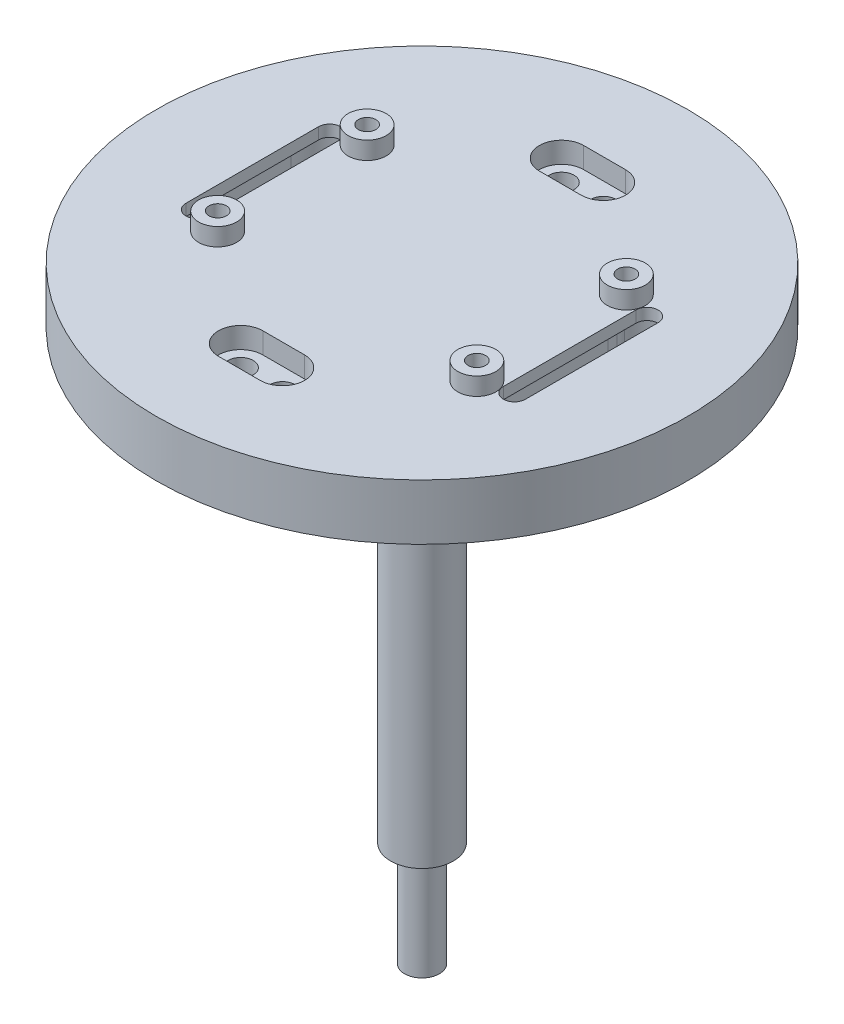
SolidWorks part; units mm, degrees
ref_plane "Front Plane" through (0, 0, 0) normal (0, 0, 1) x (1, 0, 0)
ref_plane "Top Plane" through (0, 0, 0) normal (0, 1, 0) x (1, 0, 0)
ref_plane "Right Plane" through (0, 0, 0) normal (1, 0, 0) x (0, 0, -1)
sketch "Sketch1" plane through (0, 0, 0) normal (0, 0, 1) x (1, 0, 0)
  line L0 (0, 0) -> (0, 87) construction
  line L1 (0, 87) -> (38.1, 87)
  line L2 (38.1, 87) -> (38.1, 79)
  line L3 (38.1, 79) -> (15, 79)
  line L4 (15, 79) -> (15, 80)
  line L5 (15, 80) -> (4.5, 80)
  line L6 (4.5, 80) -> (4.5, 15)
  line L7 (4.5, 15) -> (2.5, 15)
  line L8 (2.5, 15) -> (2.5, 0)
  line L9 (2.5, 0) -> (0, 0)
  line L10 (0, 0) -> (0, 87)
  dimension "D1" = 79
  dimension "D2" = 5
  dimension "D3" = 9
  dimension "D4" = 1
  dimension "D5" = 30
  dimension "D6" = 8
  dimension "D7" = 76.2
  dimension "D8" = 15
revolve "Revolve1" add sketch "Sketch1" angle 360 about L0
hole_wizard "CBORE for M3 SHCS1" positions "Sketch2" profile "Sketch3" counterbore size "M3" standard "ANSI Metric" end condition through all
sketch "Sketch2" plane through (0, 87, 0) normal (0, 1, 0) x (1, 0, 0)
  line L0 (0, 0) -> (0, 23) construction
  line L1 (0, 23) -> (3, 23) construction
  line L3 (0, 23) -> (-3, 23) construction
  line L5 (-3, -23) -> (0, -23) construction
  line L6 (0, -23) -> (0, 0) construction
  line L8 (0, -23) -> (3, -23) construction
  point P0 (3, 23)
  point P11 (-3, 23)
  point P14 (-3, -23)
  point P21 (3, -23)
  dimension "D1" = 46
  dimension "D2" = 6
sketch "Sketch3" plane through (3, 87, -23) normal (1, 0, 0) x (0, 0, 1)
  line L0 (0, 0) -> (0, 87)
  line L1 (0, 87) -> (1.8, 87)
  line L3 (1.8, 87) -> (1.8, 3)
  line L4 (1.8, 3) -> (3.175, 3)
  line L5 (3.175, 3) -> (3.175, 0)
  line L7 (3.175, 0) -> (0, 0)
  line L11 (0, -6.35) -> (0, 107.95) construction
  dimension "Thru Hole Dia." = 3.6
  dimension "Thru Hole Depth" = 87
  dimension "C'Bore Dia." = 6.35
  dimension "C'Bore Depth" = 3
sketch "Sketch4" plane through (0, 84, 0) normal (0, 1, 0) x (1, 0, 0)
  line L0 (-3, 23) -> (3, 23) construction
  line L1 (-3, 26.175) -> (3, 26.175)
  line L2 (-3, 19.825) -> (3, 19.825)
  line L3 (-3, -23) -> (3, -23) construction
  line L4 (-3, -19.825) -> (3, -19.825)
  line L5 (-3, -26.175) -> (3, -26.175)
  arc A0 (-3, 26.175) -> (-3, 19.825) centre (-3, 23) ccw
  arc A1 (3, 19.825) -> (3, 26.175) centre (3, 23) ccw
  arc A2 (0, 21.9605) -> (0, 24.0395) centre (3, 23) ccw construction
  arc A3 (-3, -19.825) -> (-3, -26.175) centre (-3, -23) ccw
  arc A4 (3, -26.175) -> (3, -19.825) centre (3, -23) ccw
  arc A5 (0, -21.9605) -> (0, -24.0395) centre (-3, -23) ccw construction
  point P4 (0, 23)
  point P16 (0, -23)
extrude "Cut-Extrude1" cut sketch "Sketch4" along normal through all
sketch "Sketch5" plane through (0, 87, 0) normal (0, 1, 0) x (1, 0, 0)
  line L0 (-22.75, -9.5) -> (-22.75, 9.5) construction
  line L1 (-24.3375, -9.5) -> (-24.3375, 9.5)
  line L2 (-21.1625, -9.5) -> (-21.1625, 9.5)
  arc A0 (-24.3375, -9.5) -> (-21.1625, -9.5) centre (-22.75, -9.5) ccw
  arc A1 (-21.1625, 9.5) -> (-24.3375, 9.5) centre (-22.75, 9.5) ccw
  point P2 (-22.75, 0)
  dimension "D1" = 22.75
  dimension "D2" = 19
  dimension "D3" = 3.175
extrude "Cut-Extrude2" cut sketch "Sketch5" against normal through all
mirror "Mirror1" about plane through (0, 0, 0) normal (1, 0, 0) of "Cut-Extrude2"
sketch "Sketch7" plane through (0, 79, 0) normal (0, -1, 0) x (1, 0, 0)
  line L0 (21.1625, -9.5) -> (21.1625, 9.5)
  line L1 (21.1625, -9.5) -> (21.1625, 9.5) construction
  line L2 (24.3375, 9.5) -> (24.3375, -9.5)
  line L3 (24.3375, 9.5) -> (24.3375, -9.5) construction
  line L4 (-21.1625, -9.5) -> (-21.1625, 9.5)
  line L5 (-21.1625, -9.5) -> (-21.1625, 9.5) construction
  line L6 (-24.3375, 9.5) -> (-24.3375, -9.5)
  line L7 (-24.3375, 9.5) -> (-24.3375, -9.5) construction
  line L8 (28.3062, 9.5) -> (28.3062, -9.5)
  line L9 (17.1938, -9.5) -> (17.1938, 9.5)
  line L10 (-17.1938, -9.5) -> (-17.1938, 9.5)
  line L11 (-28.3062, 9.5) -> (-28.3063, -9.5)
  arc A0 (24.3375, 9.5) -> (21.1625, 9.5) centre (22.75, 9.5) ccw
  arc A1 (24.3375, 9.5) -> (21.1625, 9.5) centre (22.75, 9.5) ccw construction
  arc A2 (21.1625, -9.5) -> (24.3375, -9.5) centre (22.75, -9.5) ccw
  arc A3 (21.1625, -9.5) -> (24.3375, -9.5) centre (22.75, -9.5) ccw construction
  arc A4 (-24.3375, -9.5) -> (-21.1625, -9.5) centre (-22.75, -9.5) ccw
  arc A5 (-24.3375, -9.5) -> (-21.1625, -9.5) centre (-22.75, -9.5) ccw construction
  arc A6 (-21.1625, 9.5) -> (-24.3375, 9.5) centre (-22.75, 9.5) ccw
  arc A7 (-21.1625, 9.5) -> (-24.3375, 9.5) centre (-22.75, 9.5) ccw construction
  arc A8 (17.1938, -9.5) -> (28.3062, -9.5) centre (22.75, -9.5) ccw
  arc A9 (28.3062, 9.5) -> (17.1938, 9.5) centre (22.75, 9.5) ccw
  arc A10 (-17.1938, 9.5) -> (-28.3062, 9.5) centre (-22.75, 9.5) ccw
  arc A11 (-28.3063, -9.5) -> (-17.1938, -9.5) centre (-22.75, -9.5) ccw
  dimension "D1" = 11.1125
  dimension "D2" = 11.1125
extrude "Cut-Extrude3" cut sketch "Sketch7" against normal blind 6.35
sketch "Sketch9" plane through (0, 80, 0) normal (0, -1, 0) x (1, 0, 0)
  circle A0 centre (0, 0) radius 4.5 construction
  circle A1 centre (0, 0) radius 4.5
sketch "Sketch10" plane through (0, 87, 0) normal (0, 1, 0) x (1, 0, 0)
  circle A4 centre (-0.0119, 21.4427) radius 1.75 construction
  circle A5 centre (-0.0119, 21.4427) radius 1.75 construction
  circle A12 centre (0, 0) radius 21.4431 construction
  circle A13 centre (18.5644, 10.7317) radius 1.75 construction
  circle A14 centre (18.5766, -10.7114) radius 1.75 construction
  circle A15 centre (0.0124, -21.4435) radius 1.75 construction
  circle A16 centre (-18.564, -10.7325) radius 1.75 construction
  circle A17 centre (-18.5761, 10.7106) radius 1.75 construction
  circle A18 centre (18.5644, 10.7317) radius 2.7305
  circle A19 centre (18.5766, -10.7114) radius 2.7305
  circle A20 centre (-18.564, -10.7325) radius 2.7305
  circle A21 centre (-18.5761, 10.7106) radius 2.7305
  point P15 (0.0002, -0.0004)
  dimension "D1" = 42.8862
  dimension "D3" = 5.461
  dimension "D2" = 6
extrude "Boss-Extrude1" add sketch "Sketch10" along normal blind 2.54
hole_wizard "M3x0.5 Tapped Hole1" positions "Sketch11" profile "Sketch13" tap size "M3x0.5" standard "ANSI Metric" end condition through all
sketch "Sketch11" plane through (0, 89.54, 0) normal (0, 1, 0) x (1, 0, 0)
  point P0 (-18.5761, 10.7106)
  point P3 (18.5644, 10.7317)
  point P6 (18.5766, -10.7114)
  point P9 (-18.5761, -10.7114)
sketch "Sketch13" plane through (-18.5761, 89.54, -10.7106) normal (1, 0, 0) x (0, 0, 1)
  line L0 (0, 0) -> (0, 89.54)
  line L1 (0, 89.54) -> (1.25, 89.54)
  line L2 (1.25, 89.54) -> (1.25, 0)
  line L5 (1.25, 0) -> (0, 0)
  line L11 (0, -6.35) -> (0, 107.95) construction
  dimension "Thru Tap Drill Dia." = 2.5
  dimension "Thru Tap Drill Depth" = 89.54
cosmetic thread "Hole Thread1" parameters "D2"=3
cosmetic thread "Hole Thread2" parameters "D2"=3
cosmetic thread "Hole Thread3" parameters "D2"=3
cosmetic thread "Hole Thread4" parameters "D2"=3
equation "\"mm\"=0.1"
